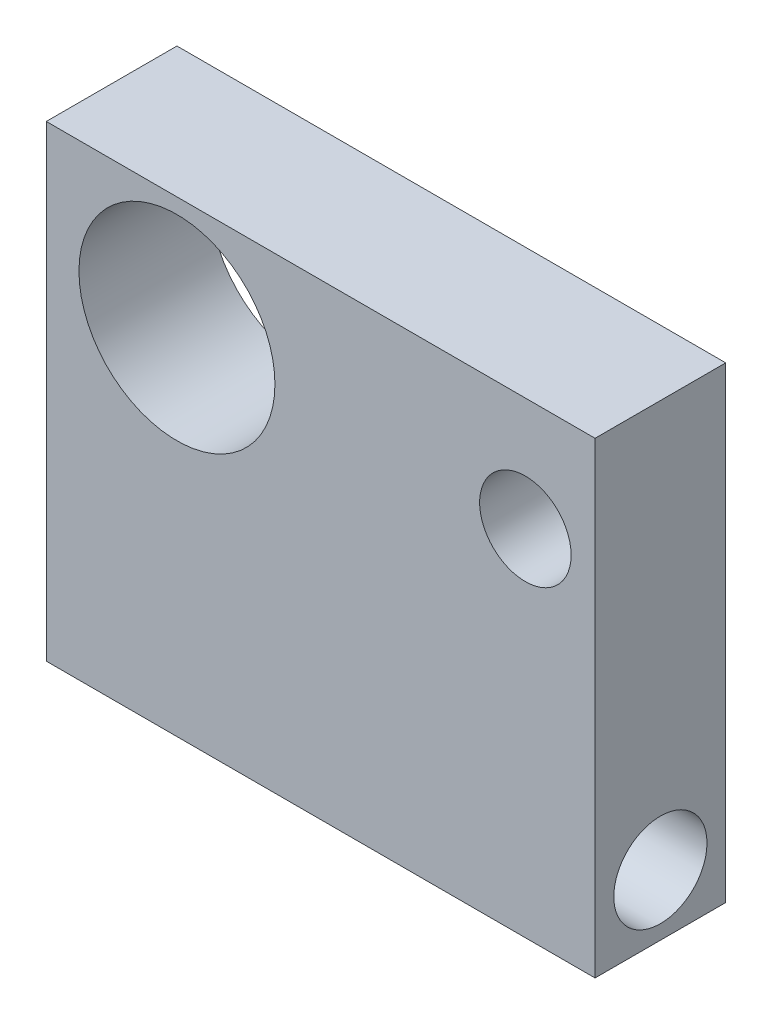
SolidWorks part; units mm, degrees
ref_plane "Front Plane" through (0, 0, 0) normal (0, 0, 1) x (1, 0, 0)
ref_plane "Top Plane" through (0, 0, 0) normal (0, 1, 0) x (1, 0, 0)
ref_plane "Right Plane" through (0, 0, 0) normal (1, 0, 0) x (0, 0, -1)
sketch "Sketch2" plane through (0, 0, 0) normal (0, 0, 1) x (1, 0, 0)
  line L1 (-31.9438, -27.208) -> (31.0562, -27.208)
  line L2 (-31.9438, -27.208) -> (-31.9438, 26.452)
  line L3 (-31.9438, 26.452) -> (31.0562, 26.452)
  line L4 (31.0562, -27.208) -> (31.0562, 26.452)
  line L5 (-31.9438, -27.208) -> (31.0562, 26.452) construction
  circle A0 centre (23.0562, 13.452) radius 5.25
  circle A1 centre (-16.9438, 13.452) radius 11.25
  point P0 (0, 0)
  dimension "D3" = 22.5
  dimension "D4" = 10.5
  dimension "D6" = 8
  dimension "D7" = 13
  dimension "D1" = 40.66
  dimension "D2" = 15
  dimension "D5" = 0
  dimension "D8" = 40
extrude "Boss-Extrude1" add sketch "Sketch2" along normal blind 15
sketch "Sketch3" plane through (31.0562, 0, 0) normal (1, 0, 0) x (0, 0, -1)
  line L0 (-15, -27.208) -> (0, -27.208) construction
  circle A0 centre (-7.5, -20.208) radius 5.35
  dimension "D1" = 10.7
  dimension "D2" = 7
extrude "Cut-Extrude1" cut sketch "Sketch3" against normal blind 20
hole_wizard "Hole2" positions "Sketch9" profile "Sketch10" legacy end condition through all
sketch "Sketch9" plane through (11.0562, 0, 0) normal (1, 0, 0) x (0, 0, -1)
  circle A0 centre (-7.5, -20.208) radius 5.35 construction
  point P0 (-7.5, -20.208)
  dimension "D1" = 0
sketch "Sketch10" plane through (11.0562, -20.208, 7.5) normal (0, 1, 0) x (0, 0, -1)
  line L0 (0, 0) -> (0, 43)
  line L1 (0, 43) -> (4.25, 43)
  line L2 (4.25, 43) -> (4.25, 0)
  line L3 (4.25, 0) -> (0, 0)
  line L4 (0, 110) -> (0, -10) construction
  dimension "Diameter" = 8.5
  dimension "Depth" = 43
